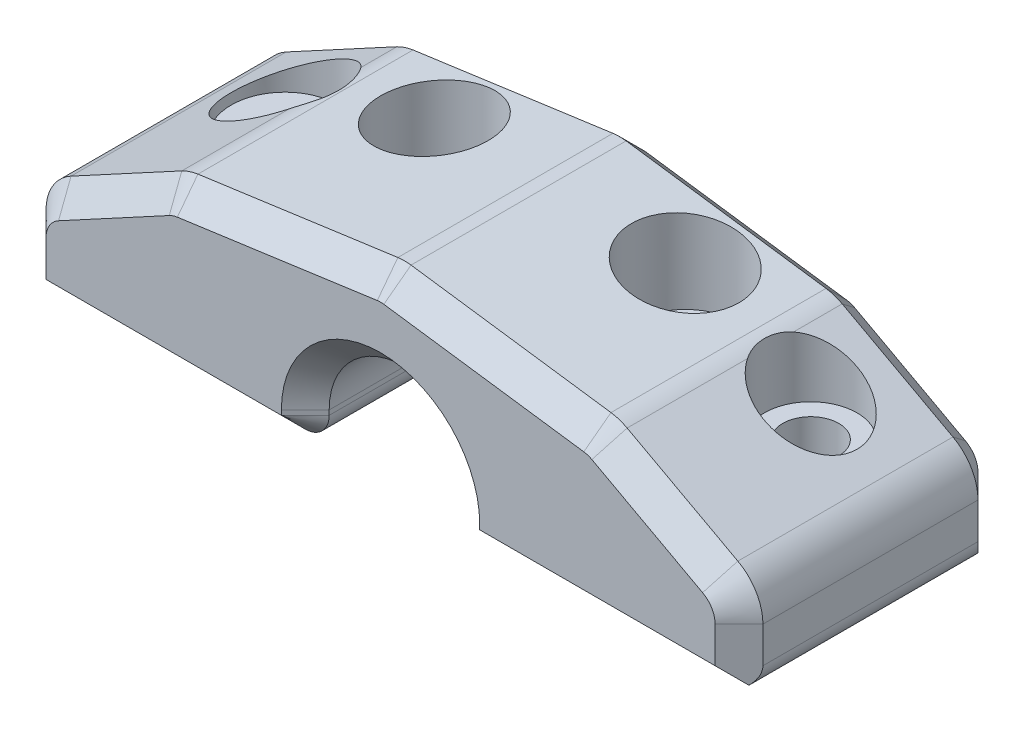
SolidWorks part; units mm, degrees
ref_plane "Front Plane" through (0, 0, 0) normal (0, 0, 1) x (1, 0, 0)
ref_plane "Top Plane" through (0, 0, 0) normal (0, 1, 0) x (1, 0, 0)
ref_plane "Right Plane" through (0, 0, 0) normal (1, 0, 0) x (0, 0, -1)
sketch "Sketch1" plane through (0, 0, 0) normal (0, 0, 1) x (1, 0, 0)
  line L0 (-3.15, 0) -> (-15, 0)
  line L1 (-15, 0) -> (-15, 7)
  line L2 (-15, 7) -> (15, 7)
  line L3 (0, 7) -> (0, 3.3) construction
  line L4 (15, 0) -> (15, 7)
  line L5 (3.15, 0) -> (15, 0)
  arc A0 (3.15, 0) -> (-3.15, 0) centre (0, 0) ccw
  dimension "D1" = 6.3
  dimension "D2" = 30
  dimension "D3" = 7
extrude "Boss-Extrude1" add sketch "Sketch1" along normal blind 11
sketch "Sketch2" plane through (0, 0, 11) normal (0, 0, 1) x (1, 0, 0)
  line L0 (0, 7) -> (-9, 5.75)
  line L1 (15, 7) -> (-15, 7) construction
  line L2 (-9, 5.75) -> (-15, 2.5044)
  line L3 (-15, 7) -> (-15, 0) construction
  line L4 (-15, 2.5044) -> (-15, 7)
  line L5 (-15, 7) -> (15, 7)
  line L6 (0, 8.1862) -> (0, -3.9101) construction
  line L7 (15, 2.5044) -> (15, 7)
  line L8 (9, 5.75) -> (15, 2.5044)
  line L9 (0, 7) -> (9, 5.75)
  line L10 (-15, 0) -> (-3.15, 0) construction
  line M8 (15, 0) -> (15, 7)
  line M9 (15, 7) -> (-15, 7)
  line M10 (-15, 7) -> (-15, 0)
  dimension "D1" = 5.75
  dimension "D2" = 18
  dimension "D3" = 4.4956
extrude "Cut-Extrude1" cut sketch "Sketch2" against normal through all both and the other way through all contours L2 L0 M9 M10 | L9 L8 M9 M8
sketch "Sketch3" plane through (0, 0, 11) normal (0, 0, 1) x (1, 0, 0)
  line L0 (-3.15, 0) -> (-3.15, -1.1963)
  line L1 (-3.15, -1.1963) -> (-15, -1.1963)
  line L2 (-15, -1.1963) -> (-15, 0)
  line L3 (-15, 0) -> (-3.15, 0)
  line L4 (0, 2.4166) -> (0, -1.9705) construction
  line L5 (15, 0) -> (3.15, 0)
  line L6 (15, -1.1963) -> (15, 0)
  line L7 (3.15, -1.1963) -> (15, -1.1963)
  line L8 (3.15, 0) -> (3.15, -1.1963)
extrude "Boss-Extrude2" add sketch "Sketch3" against normal up to surface (11 mm away) up to face at (0, 2.9621, 0)
chamfer "Chamfer1" distance 1 angle 45 4 edges at (-15, 0.6541, 0) (-15, 0.6541, 11) (15, 0.6541, 0) (15, 0.6541, 11)
fillet "Fillet1" radius 1 2 edges at (3.15, -1.1963, 5.5) (-3.15, -1.1963, 5.5)
sketch "Sketch4" plane through (0, -1.1963, 0) normal (0, -1, 0) x (1, 0, 0)
  line L0 (0, 10.0567) -> (0, -3.4815) construction
  line L1 (-5.25, 3.5) -> (5.25, 3.5) construction
  line L2 (-3.15, 0) -> (3.15, 0) construction
  circle A0 centre (-5.25, 3.5) radius 1.175
  circle A1 centre (5.25, 3.5) radius 1.175
  circle A2 centre (-11, 4) radius 1.175
  circle A3 centre (11, 4) radius 1.175
  point P8 (0, 3.5)
  point P14 (0, 0)
  point P15 (0, 0)
  point P16 (-11, 4.1883)
  dimension "D2" = 2.35
  dimension "D1" = 10.5
  dimension "D3" = 3.5
  dimension "D4" = 22
  dimension "D5" = 4
extrude "Cut-Extrude2" cut sketch "Sketch4" against normal through all
sketch "Sketch5" plane through (0, 0, 0) normal (0, 1, 0) x (1, 0, 0)
  circle A0 centre (-5.25, -3.5) radius 2.25
  circle A1 centre (5.25, -3.5) radius 2.25
  circle A2 centre (-11, -4) radius 2.25
  circle A3 centre (11, -4) radius 1.9395
  dimension "D1" = 4.5
extrude "Cut-Extrude3" cut sketch "Sketch5" along normal blind 10 from offset 3
fillet "Fillet2" radius 2 6 edges at (9, 5.75, 5.5) (-9, 5.75, 1.4846) (-9, 5.75, 8.0154) (0, 7, 5.5) (-15, 2.5044, 5.5) (15, 2.5044, 5.5)
fillet "Fillet3" radius 1 2 edges at (15, -1.1963, 5.5) (-15, -1.1963, 5.5)
chamfer "Chamfer2" distance 1 angle 45 32 edges at (-11.6349, 4.3247, 0) (-11.6349, 4.3247, 11) (-8.9899, 5.7192, 0) (-8.9899, 5.7192, 11) (-4.4584, 6.3808, 0) (-4.4584, 6.3808, 11) (11.6349, 4.3247, 11) (11.6349, 4.3247, 0) (0, 6.9808, 0) (0, 6.9808, 11) (8.9899, 5.7192, 0) (8.9899, 5.7192, 11) (4.4584, 6.3808, 11) (4.4584, 6.3808, 0) (-9.075, -1.1963, 0) (9.075, -1.1963, 0) (-3.4429, -0.9034, 0) (-3.4429, -0.9034, 11) (3.4429, -0.9034, 11) (3.4429, -0.9034, 0) (-3.15, -0.0982, 0) (3.15, -0.0982, 0) (0, 3.15, 0) (0, 3.15, 11) (-9.075, -1.1963, 11) (9.075, -1.1963, 11) (-3.15, -0.0982, 11) (3.15, -0.0982, 11) (-13.9759, 3.0582, 0) (-13.9759, 3.0582, 11) (13.9759, 3.0582, 0) (13.9759, 3.0582, 11)
